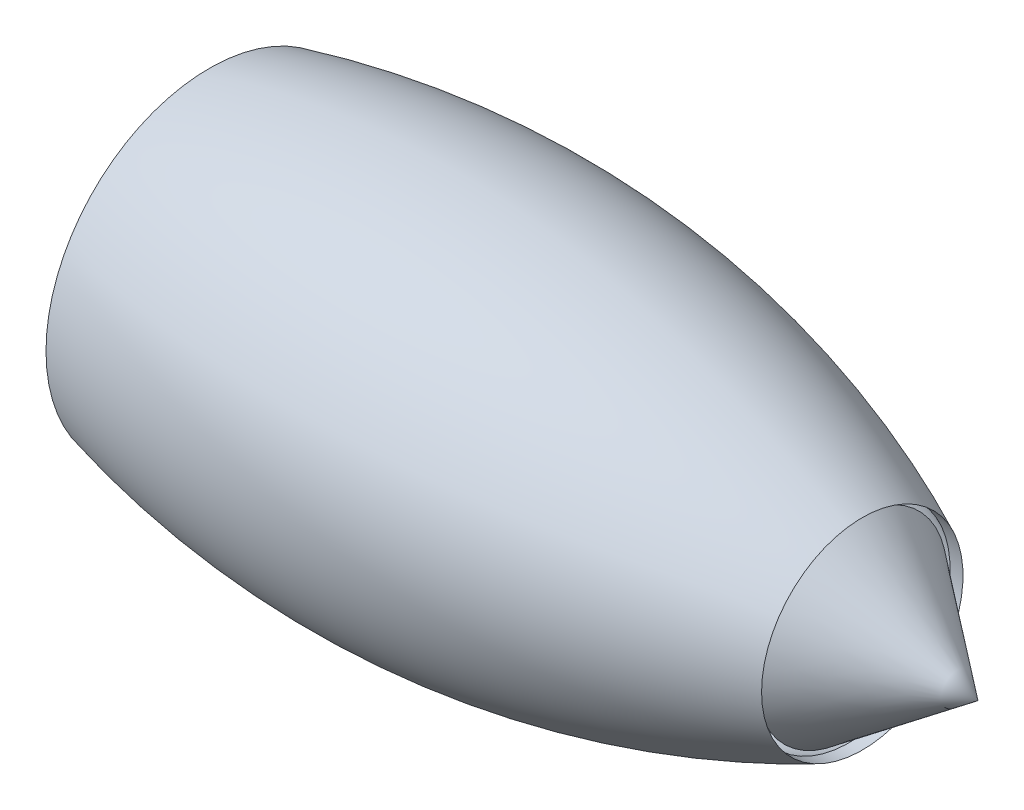
SolidWorks part; units mm, degrees
ref_plane "Front Plane" through (0, 0, 0) normal (0, 0, 1) x (1, 0, 0)
ref_plane "Top Plane" through (0, 0, 0) normal (0, 1, 0) x (1, 0, 0)
ref_plane "Right Plane" through (0, 0, 0) normal (1, 0, 0) x (0, 0, -1)
sketch "Sketch1" plane through (0, 0, 0) normal (0, 1, 0) x (1, 0, 0)
  line L0 (-100.9211, 0) -> (98.5952, 0) construction
  line L1 (-100.9211, 0) -> (-100.9211, 60)
  line L2 (153.0789, 0) -> (153.0789, 30)
  line L3 (-98.9211, 0) -> (-98.9211, 58.4376)
  line L4 (151.0789, 0) -> (151.0789, 28.7865)
  line L5 (-100.9211, 0) -> (-98.9211, 0)
  line L6 (151.0789, 0) -> (153.0789, 0)
  arc A0 (-100.9211, 60) -> (153.0789, 30) centre (-13.2734, -288.182) cw
  arc A1 (-98.9211, 58.4376) -> (151.0789, 28.7865) centre (-13.2734, -288.182) cw
  dimension "D1" = 60
  dimension "D2" = 30
  dimension "D4" = 250
  dimension "D3" = 2
revolve "Revolve1" add sketch "Sketch1" angle 360 about L6
sketch "Sketch2" plane through (-100.9211, 0, 0) normal (-1, 0, 0) x (0, 0, 1)
  circle A0 centre (0, 0) radius 57
  dimension "D1" = 114
extrude "Cut-Extrude1" cut sketch "Sketch2" against normal blind 26
sketch "Sketch3" plane through (153.0789, 0, 0) normal (1, 0, 0) x (0, 0, -1)
  circle A0 centre (0, 0) radius 37
  dimension "D1" = 74
extrude "Cut-Extrude2" cut sketch "Sketch3" against normal blind 50
fillet "Fillet1" [suppressed] radius 1.5
ref_plane "Plane1" through (135, 0, 0) normal (1, 0, 0) x (0, 0, -1)
sketch "Sketch4" plane through (135, 0, 0) normal (1, 0, 0) x (0, 0, -1)
  circle A0 centre (0, 0) radius 35
  dimension "D1" = 70
extrude "Boss-Extrude1" add sketch "Sketch4" along normal blind 50 draft 37 separate body
scale "Scale1" bodies to scale 104 103 scale about origin uniform scaling yes scale factor 3.3
